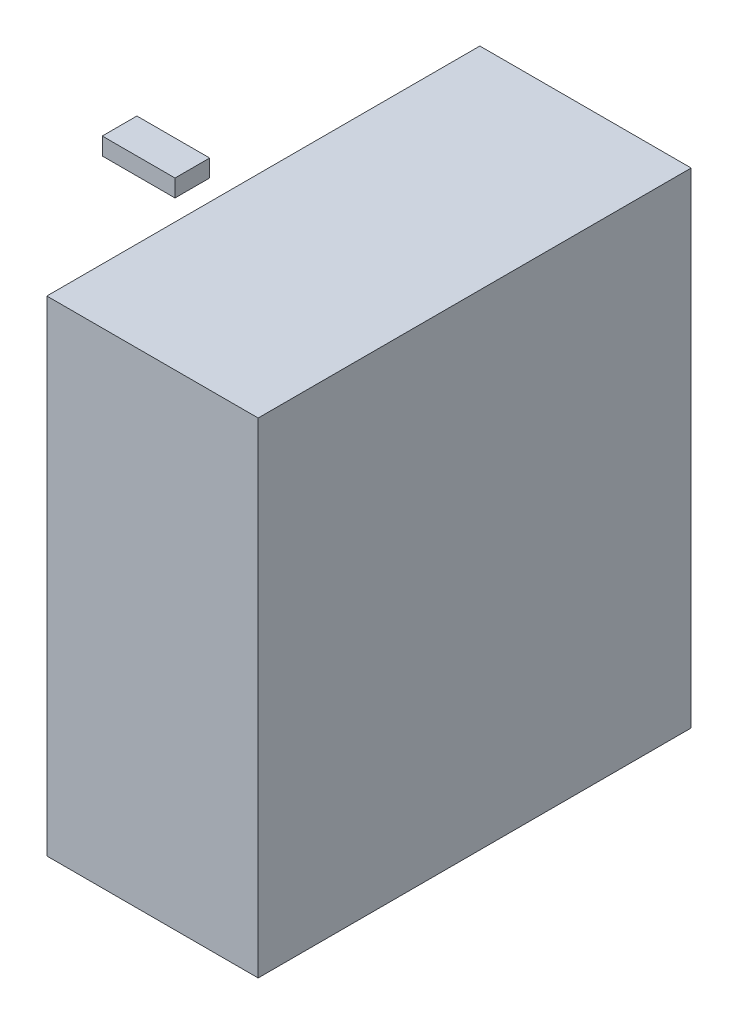
SolidWorks part; units mm, degrees
ref_plane "Front Plane" through (0, 0, 0) normal (0, 0, 1) x (1, 0, 0)
ref_plane "Top Plane" through (0, 0, 0) normal (0, 1, 0) x (1, 0, 0)
ref_plane "Right Plane" through (0, 0, 0) normal (1, 0, 0) x (0, 0, -1)
sketch "Sketch1" plane through (0, 0, 0) normal (0, 1, 0) x (1, 0, 0)
  line L7 (-2.1, -7.8) -> (0, -7.8)
  line L8 (-2.1, -7.8) -> (-2.1, -8.8)
  line L9 (-2.1, -8.8) -> (0, -8.8)
  line L10 (0, -7.8) -> (0, -8.8)
  line L11 (0, 0) -> (6.1, 0)
  line L12 (0, 0) -> (0, -12.5)
  line L13 (0, -12.5) -> (6.1, -12.5)
  line L14 (6.1, 0) -> (6.1, -12.5)
  point P0 (4.1, -6.5)
  point P1 (0, 0)
  point P10 (-2.1, -8.3)
  dimension "D1" = 2.1
  dimension "D2" = 1
  dimension "D3" = 6.5
  dimension "D4" = 1.8
  dimension "D5" = 6.1
  dimension "D6" = 12.5
  dimension "D7" = 2
extrude "Boss-Extrude1" add sketch "Sketch1" along normal blind 14 contours L14 L11 L12 L10 L13 region at (3.05, 0, 6.25)
extrude "Boss-Extrude2" add sketch "Sketch1<3>" against normal blind 0.5 from offset 0.6 contours L10 L7 L8 L9 region at (-1.05, 0, 8.3) offset against normal yes
sketch "Sketch1<3>" plane through (0, 0, 0) normal (0, 1, 0) x (1, 0, 0) same geometry as "Sketch1"
extrude "Boss-Extrude3" add sketch "Sketch1<4>" along normal blind 0.5 from offset 14.6 contours L10 L7 L8 L9 region at (-1.05, 0, 8.3)
sketch "Sketch1<4>" plane through (0, 0, 0) normal (0, 1, 0) x (1, 0, 0) same geometry as "Sketch1"
